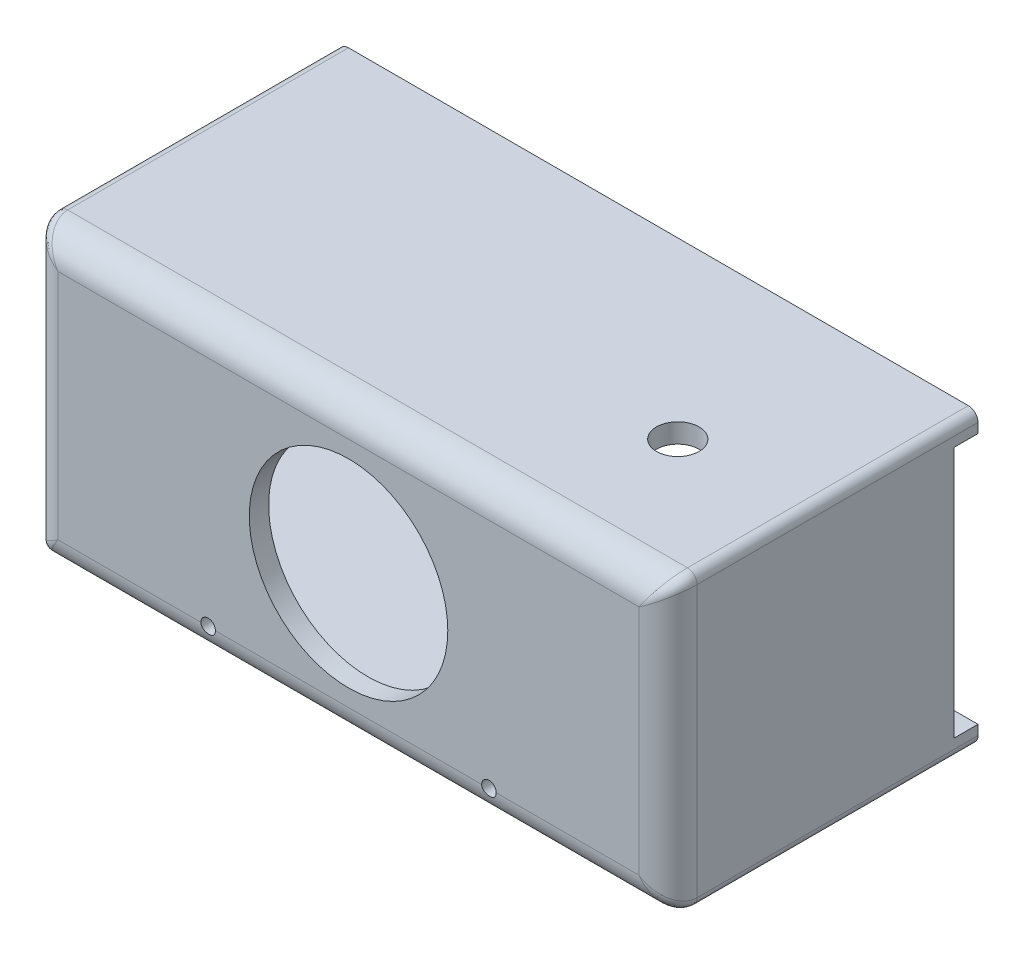
SolidWorks part; units mm, degrees
ref_plane "Front Plane" through (0, 0, 0) normal (0, 0, 1) x (1, 0, 0)
ref_plane "Top Plane" through (0, 0, 0) normal (0, 1, 0) x (1, 0, 0)
ref_plane "Right Plane" through (0, 0, 0) normal (1, 0, 0) x (0, 0, -1)
sketch "Sketch1" plane through (0, 0, 0) normal (0, 0, 1) x (1, 0, 0)
  line L1 (0, 0) -> (66, 0)
  line L2 (0, 0) -> (0, 30)
  line L3 (0, 30) -> (66, 30)
  line L4 (66, 0) -> (66, 30)
  dimension "D1" = 66
  dimension "D2" = 30
extrude "Boss-Extrude1" add sketch "Sketch1" along normal blind 2
sketch "Sketch2" plane through (0, 0, 2) normal (0, 0, 1) x (1, 0, 0)
  line L0 (0, 30) -> (0, 0) construction
  line L1 (66, 30) -> (0, 30) construction
  line L3 (0, 0) -> (66, 0) construction
  line L4 (33, 0) -> (33, 30) construction
  circle A0 centre (33, 15) radius 10.25
  circle A1 centre (18.5, 3) radius 0.75
  circle A2 centre (47.5, 3) radius 0.75
  point P4 (0, 15)
  point P7 (33, 30)
  dimension "D1" = 20.5
  dimension "D2" = 1.5
  dimension "D3" = 1.5
  dimension "D4" = 14.5
  dimension "D5" = 14.5
  dimension "D6" = 3
  dimension "D7" = 3
extrude "Cut-Extrude1" cut sketch "Sketch2" against normal through all
fillet "Fillet1" radius 1 4 edges at (66, 30, 1) (66, 0, 1) (0, 0, 1) (0, 30, 1)
sketch "Sketch3" plane through (0, 0, 0) normal (0, 0, -1) x (-1, 0, 0)
  line L8 (-66, 1) -> (-66, 29) construction
  line L9 (-1, 0) -> (-65, 0) construction
  line L10 (0, 29) -> (0, 1) construction
  line L11 (-65, 30) -> (-1, 30) construction
  line L12 (-64, 28) -> (-64, 2)
  line L13 (-64, 2) -> (-2, 2)
  line L14 (-2, 2) -> (-2, 28)
  line L15 (-2, 28) -> (-64, 28)
  line L16 (-64, 28) -> (-64, 2)
  line L17 (-64, 2) -> (-2, 2)
  line L18 (-2, 2) -> (-2, 28)
  line L19 (-2, 28) -> (-64, 28)
  line L20 (-66, 1) -> (-66, 29)
  line L21 (-1, 0) -> (-65, 0)
  line L22 (0, 29) -> (0, 1)
  line L23 (-65, 30) -> (-1, 30)
  arc A4 (-66, 1) -> (-65, 0) centre (-65, 1) ccw construction
  arc A5 (-1, 0) -> (0, 1) centre (-1, 1) ccw construction
  arc A6 (0, 29) -> (-1, 30) centre (-1, 29) ccw construction
  arc A7 (-65, 30) -> (-66, 29) centre (-65, 29) ccw construction
  arc A8 (-66, 1) -> (-65, 0) centre (-65, 1) ccw
  arc A9 (-1, 0) -> (0, 1) centre (-1, 1) ccw
  arc A10 (0, 29) -> (-1, 30) centre (-1, 29) ccw
  arc A11 (-65, 30) -> (-66, 29) centre (-65, 29) ccw
  dimension "D1" = 2
extrude "Boss-Extrude2" add sketch "Sketch3" along normal blind 30
sketch "Sketch4" plane through (0, 0, -30) normal (0, 0, -1) x (-1, 0, 0)
  line L0 (-2, 28) -> (-64, 28) construction
  line L1 (-66, 28) -> (0, 28)
  line L2 (-66, 28) -> (-66, 2)
  line L3 (-66, 2) -> (0, 2)
  line L4 (0, 28) -> (0, 2)
  line L5 (-64, 2) -> (-2, 2) construction
  line L6 (-66, 29) -> (-66, 1) construction
  point P6 (-33, 28)
  point P7 (-33, 28)
extrude "Cut-Extrude2" cut sketch "Sketch4" against normal blind 2.5
fillet "Fillet2" radius 3 8 edges at (33, 0, 2) (66, 15, 2) (0, 15, 2) (33, 30, 2) (65.7071, 29.7071, 2) (65.7071, 0.2929, 2) (0.2929, 0.2929, 2) (0.2929, 29.7071, 2)
sketch "Sketch5" plane through (0, 30, 0) normal (0, 1, 0) x (1, 0, 0)
  line L4 (33, 1) -> (33, 30) construction
  line L5 (1, 1) -> (65, 1) construction
  line L6 (1, 30) -> (65, 30) construction
  line L7 (63, -2) -> (3, -2) construction
  circle A0 centre (53, 12) radius 2.2
  dimension "D1" = 4.4
  dimension "D2" = 14
  dimension "D3" = 20
extrude "Cut-Extrude3" cut sketch "Sketch5" against normal up to next
